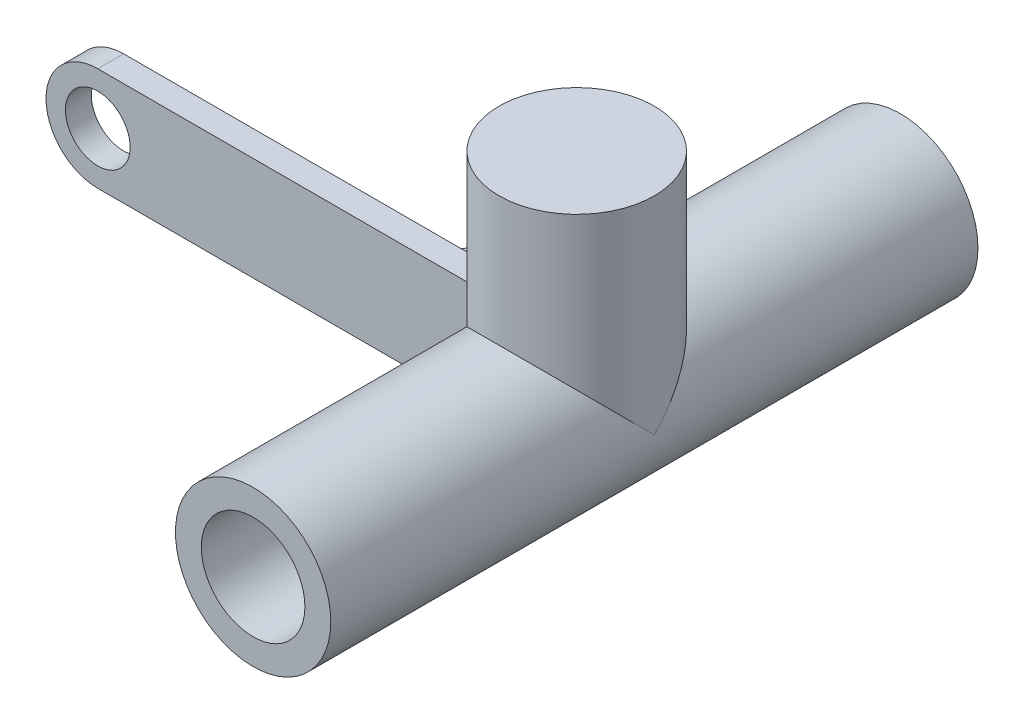
SolidWorks part; units mm, degrees
ref_plane "Front Plane" through (0, 0, 0) normal (0, 0, 1) x (1, 0, 0)
ref_plane "Top Plane" through (0, 0, 0) normal (0, 1, 0) x (1, 0, 0)
ref_plane "Right Plane" through (0, 0, 0) normal (1, 0, 0) x (0, 0, -1)
sketch "Sketch1" plane through (0, 0, 0) normal (0, 0, 1) x (1, 0, 0)
  circle A0 centre (0, 0) radius 10
  circle A1 centre (0, 0) radius 15
  dimension "D1" = 20
  dimension "D2" = 5
extrude "Boss-Extrude1" add sketch "Sketch1" along normal blind 125
sketch "Sketch2" plane through (0, 0, 0) normal (0, 1, 0) x (1, 0, 0)
  line L0 (0, 0) -> (0, -125) construction
  line L1 (-15, -125) -> (15, -125) construction
  circle A0 centre (0, -62.5) radius 15
  dimension "D1" = 30
extrude "Boss-Extrude2" add sketch "Sketch2" along normal blind 40
sketch "Sketch11" plane through (0, 0, 0) normal (1, 0, 0) x (0, 0, -1)
  line L2 (-125, -15) -> (0, -15) construction
  line L3 (-65, 10) -> (-60, 10)
  line L4 (-77.5, 40) -> (-77.5, 15) construction
  line L6 (-65, -10) -> (-60, -10)
  line L7 (-60, -10) -> (-60, 10)
  line L8 (-65, 10) -> (-65, -10)
  dimension "D1" = 20
  dimension "D2" = 5
  dimension "D3" = 5
  dimension "D4" = 12.5
extrude "Boss-Extrude6" add sketch "Sketch11" against normal blind 100
fillet "Fillet1" radius 10 2 edges at (-100, -10, 62.5) (-100, 10, 62.5)
sketch "Sketch12" plane through (0, 0, 60) normal (0, 0, -1) x (-1, 0, 0)
  line L0 (14, 1) -> (42.0346, 1)
  line L1 (14, -1) -> (42.0346, -1)
  line L3 (90, -10) -> (11.1803, -10) construction
  line L4 (14, 1) -> (14, -1)
  line L5 (0, -10) -> (0, 0) construction
  line L6 (42.0346, 1) -> (42.0346, -1)
  dimension "D1" = 2
  dimension "D2" = 9
  dimension "D3" = 14
  dimension "D4" = 28.0346
extrude "Boss-Extrude7" add sketch "Sketch12" along normal blind 30
sketch "Sketch13" plane through (0, 0, 0) normal (0, 1, 0) x (1, 0, 0)
  line L0 (-14.9666, -30) -> (-42.0346, -60)
  line L1 (-42.0346, -60) -> (-42.0346, -30)
  line L2 (-42.0346, -30) -> (-14.9666, -30)
extrude "Cut-Extrude1" cut sketch "Sketch13" against normal blind 5 and the other way blind 23 contours L2 L0 L1
sketch "Sketch16" plane through (0, 0, 60) normal (0, 0, -1) x (-1, 0, 0)
  circle A0 centre (90, 0) radius 6.25
  dimension "D2" = 12.5
extrude "Cut-Extrude2" cut sketch "Sketch16" against normal blind 7
